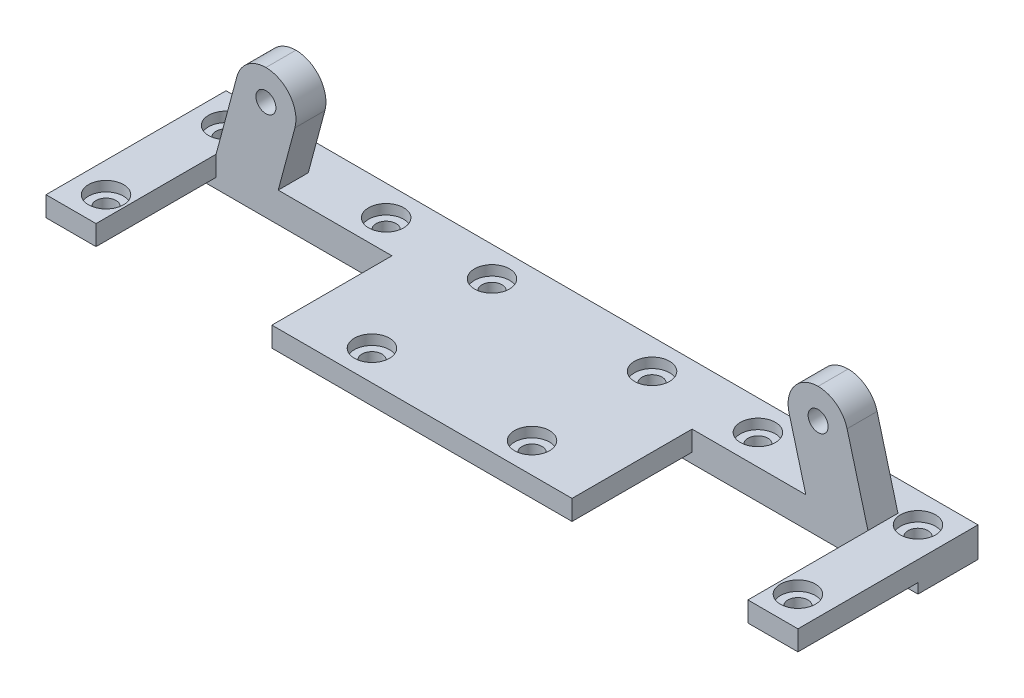
SolidWorks part; units mm, degrees
ref_plane "前视基准面" through (0, 0, 0) normal (0, 0, 1) x (1, 0, 0)
ref_plane "上视基准面" through (0, 0, 0) normal (0, 1, 0) x (1, 0, 0)
ref_plane "右视基准面" through (0, 0, 0) normal (1, 0, 0) x (0, 0, -1)
other "Configuration Table"
sketch "草图1" plane through (0, 0, 0) normal (0, 0, 1) x (1, 0, 0)
  line L3 (0, 0) -> (0, -30) construction
  line L5 (-2.8978, 0.7765) -> (-32.5802, -110)
  line L6 (2.8978, 0.7765) -> (32.5802, -110)
  line L8 (-26.3686, -110) -> (2.8978, -0.7765)
  line L10 (26.3686, -110) -> (-2.8978, -0.7765)
  line L12 (-32.5802, -110) -> (-26.3686, -110)
  line L13 (26.3686, -110) -> (32.5802, -110)
  line L14 (-16.5632, -50.2235) -> (-10.7676, -51.7765) construction
  line L15 (10.7676, -51.7765) -> (16.5632, -50.2235) construction
  circle A0 centre (0, 0) radius 3
  circle A4 centre (13.6654, -51) radius 0.75
  circle A5 centre (-13.6654, -51) radius 0.75
  circle A6 centre (0, 0) radius 0.75
  dimension "D1" = 6
  dimension "D2" = 15
  dimension "D4" = 1.5
  dimension "D5" = 110
  dimension "D6" = 51
  dimension "D3" = 15
extrude "凸台-拉伸1" add sketch "草图1" along normal blind 6 contours A0 | L6 A0 L8 L10 | L8 L10 A0 L5 | L3 A0 L10 | A0 L3 L8 region at (-1.7746, -2.3127, 0) region at (0.876, -5.5523, 0) region at (-0.876, -5.5523, 0) region at (15.5609, -57.8578, 0) region at (-15.5609, -57.8578, 0)
sketch "草图2" plane through (0, 0, 0) normal (0, 0, -1) x (-1, 0, 0)
  circle A0 centre (0, 0) radius 1
  circle A1 centre (13.6654, -51) radius 1
  circle A2 centre (-13.6654, -51) radius 1
  circle A3 centre (-13.6654, -51) radius 0.75 construction
  circle A4 centre (13.6654, -51) radius 0.75 construction
  circle A5 centre (0, 0) radius 0.75 construction
  dimension "D1" = 2
extrude "切除-拉伸1" cut sketch "草图2" against normal blind 1.5 contours A2 | A1 | A0
sketch "草图3" plane through (0, -110, 0) normal (0, -1, 0) x (1, 0, 0)
  line L0 (26.3686, 6) -> (32.5802, 6) construction
  line L1 (37.5802, -6) -> (-37.5802, -6)
  line L2 (37.5802, -6) -> (37.5802, 6)
  line L3 (37.5802, 6) -> (-37.5802, 6)
  line L4 (-37.5802, -6) -> (-37.5802, 6)
  line L5 (26.3686, 0) -> (32.5802, 0) construction
  line L6 (32.5802, 6) -> (32.5802, 0) construction
  line L7 (-32.5802, 6) -> (-32.5802, 0) construction
  dimension "D1" = 6
  dimension "D2" = 5
  dimension "D3" = 5
extrude "凸台-拉伸2" add sketch "草图3" along normal blind 3
sketch "草图4" plane through (0, 0, 6) normal (0, 0, 1) x (1, 0, 0)
  line L0 (37.5802, -113) -> (-37.5802, -113) construction
  line L1 (-30.7046, -103) -> (-24.4929, -103) construction
  line L2 (-2.8978, 0.7765) -> (-32.5802, -110) construction
  line L3 (-26.3686, -110) -> (0, -11.5911) construction
  line L4 (24.4929, -103) -> (30.7046, -103) construction
  line L5 (26.3686, -110) -> (0, -11.5911) construction
  line L6 (2.8978, 0.7765) -> (32.5802, -110) construction
  circle A0 centre (-27.5988, -103) radius 0.75
  circle A1 centre (27.5988, -103) radius 0.75
  dimension "D1" = 1.5
  dimension "D2" = 10
extrude "切除-拉伸2" cut sketch "草图4" against normal blind 3
sketch "草图5" plane through (0, -110, 0) normal (0, 1, 0) x (1, 0, 0)
  line L0 (-37.5802, 6) -> (37.5802, 6) construction
  line L1 (-37.5802, 6) -> (-32.5802, 6)
  line L2 (-37.5802, 6) -> (-37.5802, -6)
  line L3 (-37.5802, -6) -> (-32.5802, -6)
  line L4 (-32.5802, 6) -> (-32.5802, -6)
  line L5 (-37.5802, -6) -> (-37.5802, 6) construction
  line L6 (-2.8978, -6) -> (-32.5802, -6) construction
  line L7 (-32.5802, -6) -> (-37.5802, -6) construction
  line L8 (37.5802, 6) -> (37.5802, -6) construction
  line L9 (37.5802, 6) -> (32.5802, 6)
  line L10 (37.5802, 6) -> (37.5802, -6)
  line L11 (37.5802, -6) -> (32.5802, -6)
  line L12 (32.5802, 6) -> (32.5802, -6)
  line L13 (32.5802, -6) -> (32.5802, 0) construction
  line L14 (2.8978, -6) -> (32.5802, -6) construction
  line L15 (-15, 6) -> (15, 6)
  line L16 (-15, 6) -> (-15, -6)
  line L17 (-15, -6) -> (15, -6)
  line L18 (15, 6) -> (15, -6)
  line L19 (-32.5802, -6) -> (-32.5802, 0) construction
  line L20 (37.5802, -6) -> (32.5802, -6) construction
  line L21 (0, 0) -> (0, 6) construction
  line L22 (2.8978, 0) -> (-2.8978, 0) construction
  dimension "D1" = 30
extrude "切除-拉伸3" cut sketch "草图5" against normal blind 2
sketch "草图6" plane through (0, 0, 0) normal (0, 0, -1) x (-1, 0, 0)
  line L0 (37.5802, -113) -> (-37.5802, -113) construction
  line L1 (-37.5802, -113) -> (37.5802, -113)
  line L2 (-37.5802, -113) -> (-37.5802, -100)
  line L3 (-37.5802, -100) -> (37.5802, -100)
  line L4 (37.5802, -113) -> (37.5802, -100)
  line L5 (-37.5802, -113) -> (-37.5802, -112) construction
  line L6 (37.5802, -113) -> (37.5802, -112) construction
  dimension "D1" = 13
extrude "切除-拉伸4" cut sketch "草图6" against normal through all flip side to cut
sketch "草图7" plane through (37.5802, 0, 0) normal (1, 0, 0) x (0, 0, -1)
  line L1 (-3, -100) -> (6, -100)
  line L2 (-3, -100) -> (-3, -113)
  line L3 (-3, -113) -> (6, -113)
  line L4 (6, -100) -> (6, -113)
  line L5 (6, -113) -> (6, -112) construction
  line L6 (-6, -100) -> (-6, -110) construction
  line L7 (6, -113) -> (-6, -113) construction
  line L8 (0, -100) -> (-6, -100) construction
  dimension "D1" = 3
extrude "切除-拉伸5" cut sketch "草图7" against normal through all
sketch "草图8" plane through (0, 0, 3) normal (0, 0, -1) x (-1, 0, 0)
  circle A0 centre (-27.5988, -103) radius 1.75
  circle A1 centre (-27.5988, -103) radius 1
  circle A2 centre (27.5988, -103) radius 1.75
  circle A3 centre (27.5988, -103) radius 1
  circle A4 centre (-27.5988, -103) radius 0.75 construction
  circle A5 centre (27.5988, -103) radius 0.75 construction
  dimension "D1" = 2
  dimension "D2" = 3.5
extrude "切除-拉伸6" cut sketch "草图8" against normal through all contours A1 | A3
extrude "切除-拉伸7" cut sketch "草图8<3>" against normal blind 1.5
sketch "草图8<3>" plane through (0, 0, 3) normal (0, 0, -1) x (-1, 0, 0) same geometry as "草图8"
sketch "草图9" plane through (0, -112, 0) normal (0, 1, 0) x (1, 0, 0)
  line L1 (37.5802, -18) -> (32.5802, -18)
  line L2 (37.5802, -18) -> (37.5802, -3)
  line L3 (37.5802, -3) -> (32.5802, -3)
  line L4 (32.5802, -18) -> (32.5802, -3)
  line L5 (37.5802, -6) -> (37.5802, -3) construction
  line L6 (29.9007, -3) -> (32.5802, -3) construction
  line L7 (37.5802, -3) -> (32.5802, -3) construction
  line L9 (15, -18) -> (-15, -18)
  line L10 (15, -18) -> (15, -3)
  line L11 (15, -3) -> (-15, -3)
  line L12 (-15, -18) -> (-15, -3)
  line L14 (-15, -3) -> (15, -3) construction
  line L16 (-32.5802, -18) -> (-37.5802, -18)
  line L17 (-32.5802, -18) -> (-32.5802, -3)
  line L18 (-32.5802, -3) -> (-37.5802, -3)
  line L19 (-37.5802, -18) -> (-37.5802, -3)
  line L21 (-37.5802, -3) -> (-37.5802, -6) construction
  line L22 (32.5802, -3) -> (32.5802, -6) construction
  line L23 (-15, -3) -> (-15, -6) construction
  line L24 (-37.5802, -3) -> (-32.5802, -3) construction
  line L25 (15, -6) -> (15, -3) construction
  line L29 (-32.5802, -6) -> (-32.5802, -3) construction
  dimension "D1" = 15
extrude "凸台-拉伸3" add sketch "草图9" along normal blind 2
sketch "草图10" plane through (0, 0, 3) normal (0, 0, -1) x (-1, 0, 0)
  line L0 (-37.5802, -110) -> (-37.5802, -113) construction
  line L1 (-37.5802, -110) -> (37.5802, -110)
  line L2 (-37.5802, -110) -> (-37.5802, -113)
  line L3 (-37.5802, -113) -> (37.5802, -113)
  line L4 (37.5802, -110) -> (37.5802, -113)
  line L5 (-37.5802, -110) -> (-32.5802, -110) construction
  line L6 (37.5802, -110) -> (37.5802, -113) construction
  line L7 (37.5802, -113) -> (-37.5802, -113) construction
extrude "凸台-拉伸4" add sketch "草图10" along normal blind 3
sketch "草图11" plane through (0, -110, 0) normal (0, 1, 0) x (1, 0, 0)
  line L0 (-37.5802, 0) -> (-37.5802, -18) construction
  line L1 (-37.5802, 0) -> (37.5802, 0) construction
  line L2 (-37.5802, -18) -> (-32.5802, -18) construction
  line L3 (37.5802, -18) -> (37.5802, 0) construction
  circle A0 centre (34.5802, -15) radius 1.75
  circle A1 centre (34.5802, -15) radius 1
  circle A2 centre (34.5802, -3) radius 1.75
  circle A3 centre (34.5802, -3) radius 1
  circle A4 centre (18.5802, -3) radius 1.75
  circle A5 centre (-18.5802, -3) radius 1.75
  circle A6 centre (-18.5802, -3) radius 1
  circle A7 centre (18.5802, -3) radius 1
  circle A8 centre (-34.5802, -3) radius 1.75
  circle A9 centre (-34.5802, -3) radius 1
  circle A10 centre (-34.5802, -15) radius 1.75
  circle A11 centre (-34.5802, -15) radius 1
  circle A12 centre (18.5802, -15) radius 1.75
  circle A13 centre (18.5802, -15) radius 1
  circle A14 centre (-18.5802, -15) radius 1.75
  circle A15 centre (-18.5802, -15) radius 1
  circle A16 centre (-8, -3) radius 1
  circle A17 centre (-8, -3) radius 1.75
  circle A18 centre (8, -3) radius 1.75
  circle A19 centre (8, -3) radius 1
  circle A20 centre (-8, -15) radius 1.75
  circle A21 centre (-8, -15) radius 1
  circle A22 centre (8, -15) radius 1.75
  circle A23 centre (8, -15) radius 1
  point P37 (0, 0)
  point P38 (0, 0)
  point P39 (0, 0)
  point P40 (0, 0)
  point P41 (0, 0)
  point P42 (0, 0)
  point P47 (0, 0)
  point P50 (0, 0)
  point P51 (-20.9037, 5.3037)
  point P52 (14.8299, -3)
  point P55 (0, 0)
  dimension "D8" = 2
  dimension "D9" = 3.5
  dimension "D1" = 8
  dimension "D2" = 8
  dimension "D3" = 16
  dimension "D4" = 3
  dimension "D5" = 16
  dimension "D6" = 3
  dimension "D7" = 3
  dimension "D10" = 3
extrude "切除-拉伸8" cut sketch "草图11" against normal through all contours A9 | A11 | A15 | A21 | A23 | A13 | A1 | A3 | A7 | A19 | A16 | A6
extrude "切除-拉伸9" cut sketch "草图11<3>" against normal blind 1
sketch "草图11<3>" plane through (0, -110, 0) normal (0, 1, 0) x (1, 0, 0) same geometry as "草图11"
fillet "圆角1" radius 3 4 edges at (-29.9007, -100, 4.5) (-23.6891, -100, 4.5) (23.6891, -100, 4.5) (29.9007, -100, 4.5)
